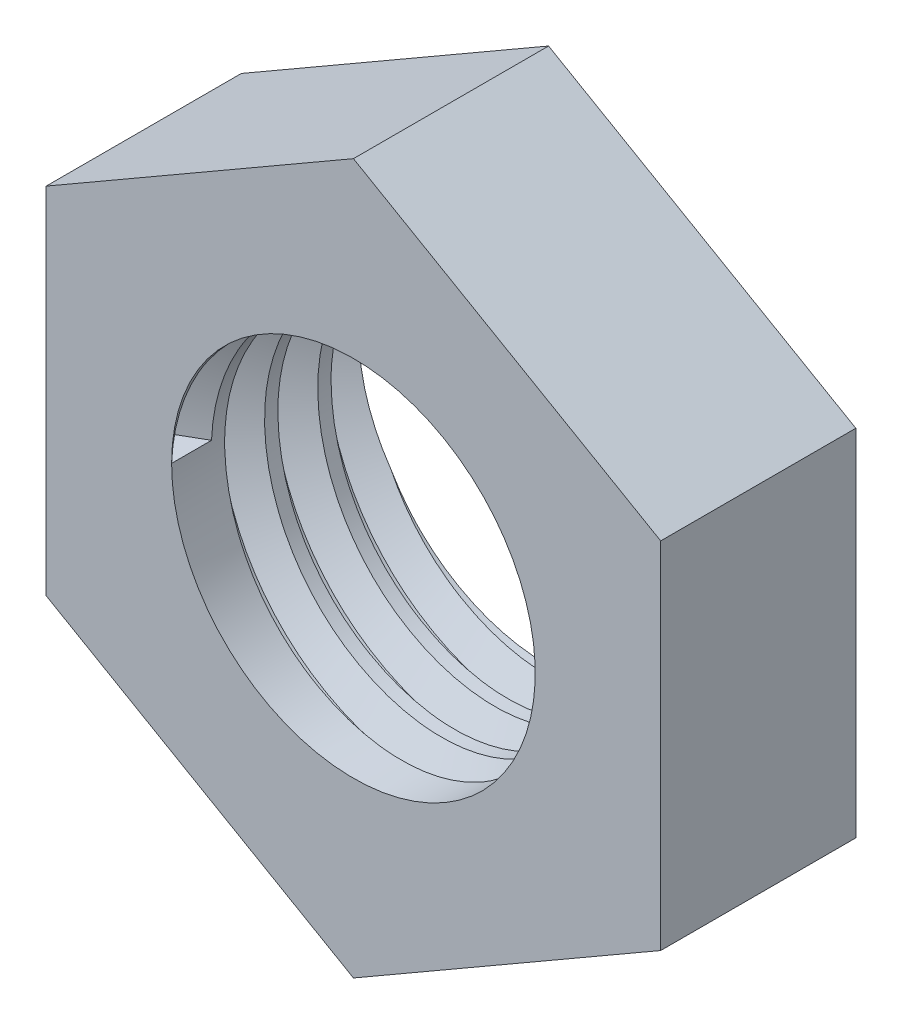
SolidWorks part; units mm, degrees
ref_plane "Front Plane" through (0, 0, 0) normal (0, 0, 1) x (1, 0, 0)
ref_plane "Top Plane" through (0, 0, 0) normal (0, 1, 0) x (1, 0, 0)
ref_plane "Right Plane" through (0, 0, 0) normal (1, 0, 0) x (0, 0, -1)
sketch "Sketch1" plane through (0, 0, 0) normal (0, 0, 1) x (1, 0, 0)
  line L1 (-3.4641, -2) -> (0, -4)
  line L2 (0, -4) -> (3.4641, -2)
  line L3 (3.4641, -2) -> (3.4641, 2)
  line L4 (3.4641, 2) -> (0, 4)
  line L5 (0, 4) -> (-3.4641, 2)
  line L6 (-3.4641, 2) -> (-3.4641, -2)
  circle A0 centre (0, 0) radius 3.4641 construction
  circle A1 centre (0, 0) radius 2.05
  dimension "D1" = 8
  dimension "D2" = 4.1
extrude "Boss-Extrude1" add sketch "Sketch1" along normal blind 2.2
thread "Thread1" pitch 0.6 method cut profile "Thread Profile1" start angle 0, offset 0, length 0, pitch 0.6, diameter 4.1
ref_plane "Plane1" through (-2.05, 0, 2.2) normal (0, -1, 0) x (-1, 0, 0)
sketch "Thread Profile1" plane through (-2.05, 0, 2.2) normal (0, -1, 0) x (-1, 0, 0)
  line L0 (0, 0) -> (0, 0.6) construction
  line L1 (0, 0) -> (0.3248, 0.1875)
  line L2 (0.3248, 0.1875) -> (0.3248, 0.2625)
  line L3 (0.3248, 0.2625) -> (0, 0.45)
  line L4 (0.3248, 0.225) -> (0, 0.225) construction
  line L11 (0, 0) -> (0, 0.45)
  point P2 (0, 0)
  dimension "Pitch" = 0.6
  dimension "Profile_Angle" = 60
  dimension "Profile_Land" = 0.075
  dimension "Profile_Height" = 0.3248
